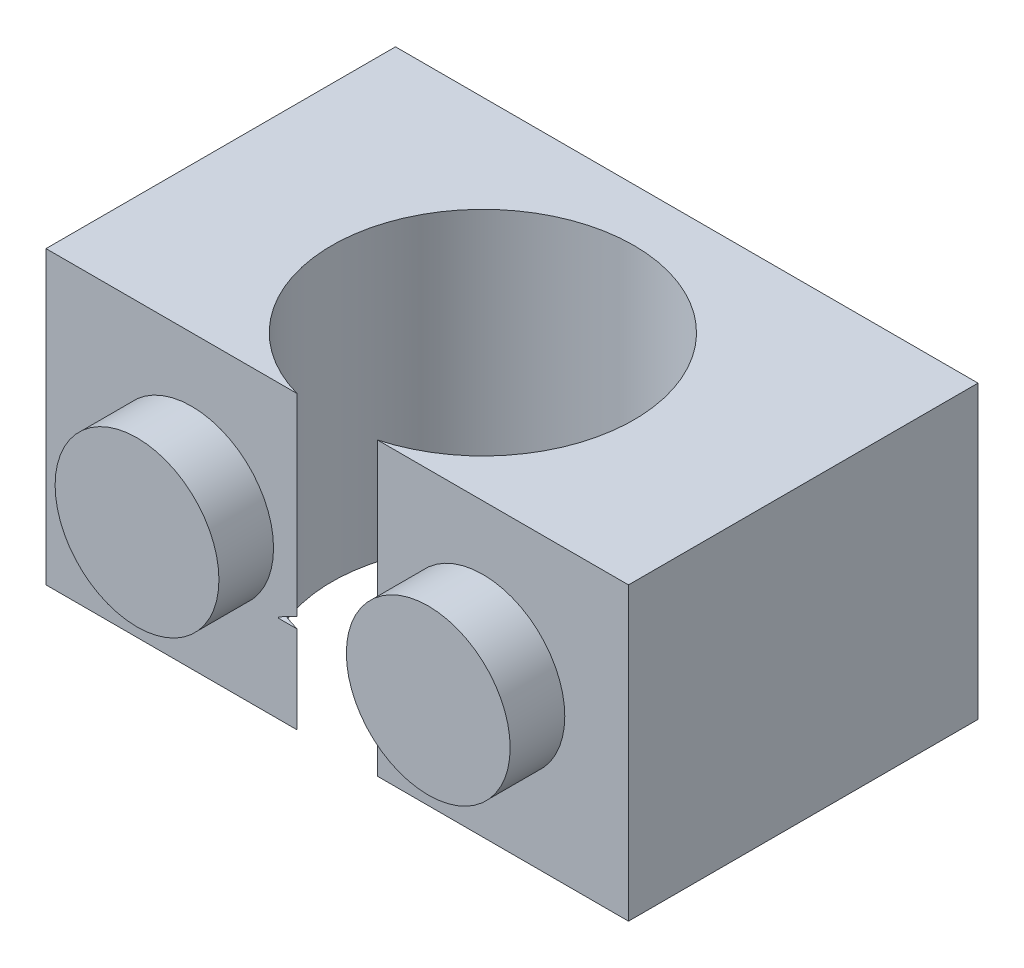
SolidWorks part; units mm, degrees
ref_plane "Front Plane" through (0, 0, 0) normal (0, 0, 1) x (1, 0, 0)
ref_plane "Top Plane" through (0, 0, 0) normal (0, 1, 0) x (1, 0, 0)
ref_plane "Right Plane" through (0, 0, 0) normal (1, 0, 0) x (0, 0, -1)
sketch "Sketch1" plane through (0, -47.1987, 0) normal (0, 1, 0) x (1, 0, 0)
  line L0 (24, 8.8545) -> (8, 8.8545) construction
  line L1 (8, 18.4545) -> (24, 18.4545) construction
  line L2 (24, 8.8545) -> (8, 8.8545) construction
  line L3 (8, 18.4545) -> (24, 18.4545) construction
  line L5 (8, 8.8545) -> (24, 8.8545)
  line L6 (8, 8.8545) -> (8, 18.4545)
  line L7 (8, 18.4545) -> (24, 18.4545)
  line L8 (24, 8.8545) -> (24, 18.4545)
  circle A0 centre (16, 12.8545) radius 4 construction
  circle A1 centre (16, 12.8545) radius 4 construction
  circle A2 centre (16, 12.8545) radius 4.15
  circle M2 centre (16, 12.8545) radius 5.225
  dimension "D1" = 0.15
extrude "Boss-Extrude1" add sketch "Sketch1" along normal blind 8 contours L5 L8 L7 L6 M2 | A2 L5 M2 region at (8.1866, -47.1987, -13.6544) region at (13.8525, -47.1987, -17.4644)
ref_plane "Plane1" through (16, 0, 0) normal (-1, 0, 0) x (0, 0, 1)
sketch "Sketch2" plane through (16, 0, 0) normal (-1, 0, 0) x (0, 0, 1)
  line L0 (-17.0894, -44.7987) -> (-8.6194, -44.7987) construction
  line L1 (-11.455, -44.2637) -> (-16.8544, -44.2637) construction
  line L2 (-14.2539, -44.2637) -> (-8.8544, -44.2637) construction
  line L3 (-17.0894, -44.7987) -> (-8.6194, -44.7987) construction
  line L4 (-11.455, -44.2637) -> (-16.8544, -44.2637)
  line L5 (-14.2539, -44.2637) -> (-8.8544, -44.2637) construction
  line L6 (-8.8544, -44.2637) -> (-8.6194, -44.7677)
  line L7 (-8.6194, -44.7677) -> (-8.6194, -44.7987)
  line L8 (-8.8544, -44.2637) -> (-8.8544, -44.7987)
  line L9 (-8.6194, -44.7987) -> (-8.8544, -44.7987)
  line L14 (-14.2539, -46.259) -> (-14.2539, -50046.259) construction
revolve "Cut-Revolve1" cut sketch "Sketch2" angle 360 about L14
sketch "Sketch3" plane through (0, 0, -8.8545) normal (0, 0, 1) x (1, 0, 0)
  circle A0 centre (20, -43.1987) radius 2.4 construction
  circle A1 centre (12, -43.1987) radius 2.4 construction
  circle A2 centre (20, -43.1987) radius 2.4 construction
  circle A3 centre (12, -43.1987) radius 2.4 construction
  circle A4 centre (12, -43.1987) radius 2.55
  circle A5 centre (12, -43.1987) radius 2.25
  circle A6 centre (20, -43.1987) radius 2.55
  circle A7 centre (20, -43.1987) radius 2.25
  dimension "D1" = 0.15
  dimension "D2" = 0.15
extrude "Boss-Extrude2" add sketch "Sketch3" along normal blind 1.5 contours A5 | A7 region at (12, -43.1987, -8.8544) region at (20, -43.1987, -8.8544)
extrude "Cut-Extrude1" cut sketch "Sketch3<3>" along normal blind 1.5 from surface contours A4 | A6 starting at face at (16, -43.1987, -18.4544)
sketch "Sketch3<3>" plane through (0, 0, -8.8545) normal (0, 0, 1) x (1, 0, 0) same geometry as "Sketch3"
